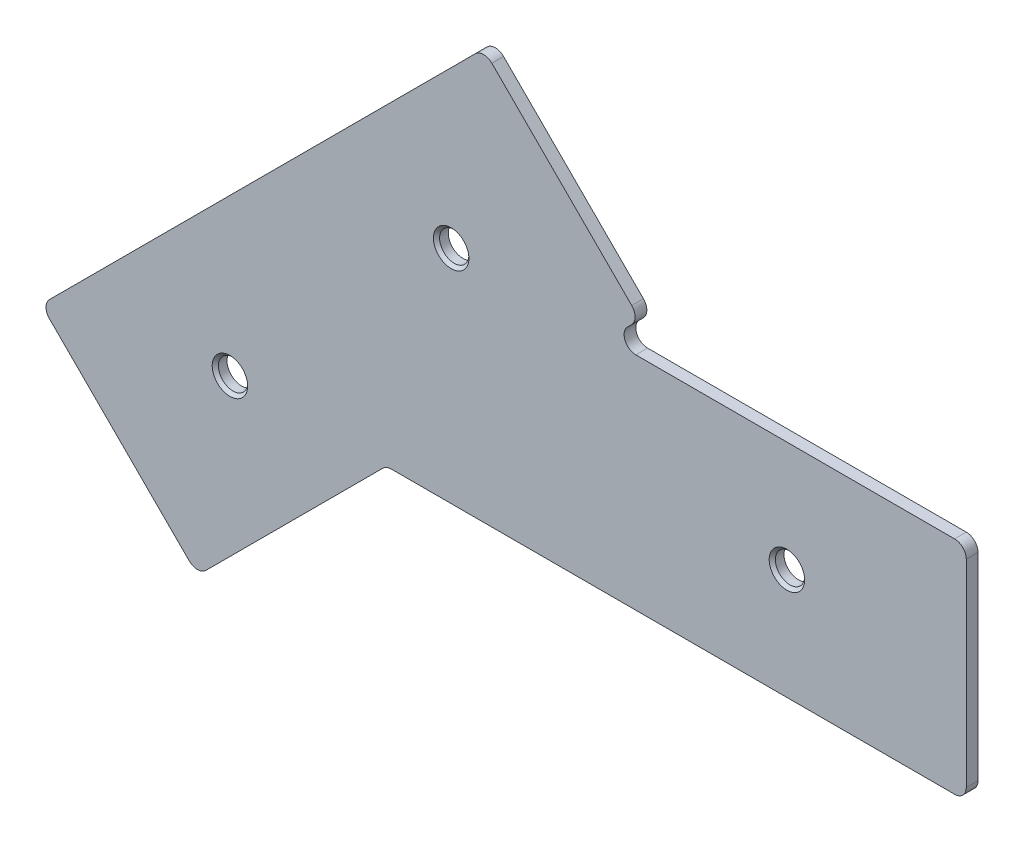
SolidWorks part; units mm, degrees
ref_plane "Front Plane" through (0, 0, 0) normal (0, 0, 1) x (1, 0, 0)
ref_plane "Top Plane" through (0, 0, 0) normal (0, 1, 0) x (1, 0, 0)
ref_plane "Right Plane" through (0, 0, 0) normal (1, 0, 0) x (0, 0, -1)
sketch "Sketch1" plane through (0, 0, 0) normal (0, 0, 1) x (1, 0, 0)
  line L0 (0, 0) -> (75.519, 75.519) construction
  line L1 (0, 0) -> (75.519, 0) construction
  line L2 (75.519, 75.519) -> (75.519, 0) construction
  line L3 (37.7595, 37.7595) -> (144.5595, 37.7595) construction
  line L4 (13.3466, -13.3466) -> (45.5778, 18.8845)
  line L5 (45.5778, 18.8845) -> (144.5595, 18.8845)
  line L6 (-13.3466, 13.3466) -> (62.1724, 88.8656)
  line L7 (37.7595, 18.8845) -> (144.5595, 18.8845) construction
  line L8 (83.3278, 56.6345) -> (144.5595, 56.6345)
  line L9 (83.3278, 56.6345) -> (88.8656, 62.1724)
  line L10 (13.3466, -13.3466) -> (88.8656, 62.1724) construction
  line L11 (-13.3466, 13.3466) -> (13.3466, -13.3466)
  line L12 (62.1724, 88.8656) -> (88.8656, 62.1724)
  line L13 (144.5595, 56.6345) -> (144.5595, 18.8845)
  dimension "D1" = 135
  dimension "D2" = 106.8
  dimension "D3" = 106.8
  dimension "D4" = 18.875
  dimension "D6" = 61.2317
  dimension "D5" = 18.875
base flange "Base-Flange1" sketch "Sketch1" thickness 2 reverse thickness direction no parameters "D1"=2
sketch "Sketch6" plane through (0, 0, 0) normal (0, 0, 1) x (1, 0, 0)
  line L0 (0, 0) -> (75.519, 75.519) construction
  line L1 (88.8656, 62.1724) -> (62.1724, 88.8656) construction
  line L2 (144.5595, 37.7595) -> (11.0662, 37.7595) construction
  line L3 (144.5595, 18.8845) -> (144.5595, 56.6345) construction
  line L4 (62.1724, 88.8656) -> (-13.3466, 13.3466) construction
  line L5 (32.2264, 5.5331) -> (5.5331, 32.2264) construction
  line L6 (13.3466, -13.3466) -> (45.5778, 18.8845) construction
  line L7 (-13.3466, 13.3466) -> (13.3466, -13.3466) construction
  line L8 (43.2926, 69.9859) -> (69.9859, 43.2926) construction
  line L9 (83.3278, 56.6345) -> (88.8656, 62.1724) construction
  line L10 (113.9436, 56.6345) -> (113.9436, 18.8845) construction
  line L11 (144.5595, 56.6345) -> (83.3278, 56.6345) construction
  line L12 (45.5778, 18.8845) -> (144.5595, 18.8845) construction
  dimension "D1" = 26.7
  dimension "D2" = 26.7
sketch "Sketch10" plane through (0, 0, 0) normal (0, 0, 1) x (1, 0, 0)
  line L0 (43.2926, 69.9859) -> (69.9859, 43.2926) construction
  line L1 (32.2264, 5.5331) -> (5.5331, 32.2264) construction
  line L2 (113.9436, 56.6345) -> (113.9436, 18.8845) construction
  point P0 (56.6393, 56.6393)
  point P4 (18.8798, 18.8798)
  point P8 (113.9436, 37.7595)
hole_wizard "M6x1.0 Tapped Hole1" positions "Sketch10" profile "Sketch8" tap size "M6x1.0" standard "ANSI Metric"
sketch "Sketch8" plane through (56.6393, 56.6393, 0) normal (1, 0, 0) x (0, -1, 0)
  line L0 (0, 0) -> (0, 16.5022)
  line L1 (0, 16.5022) -> (2.5, 15)
  line L2 (2.5, 15) -> (2.5, 0.525)
  line L3 (2.5, 0.525) -> (3.025, 0)
  line L5 (3.025, 0) -> (0, 0)
  line L6 (-2.5, 0.525) -> (-3.025, 0) construction
  line L10 (0, 16.5022) -> (-2.5, 15) construction
  line L11 (0, -6.35) -> (0, 107.95) construction
  dimension "Tap Drill Dia." = 5
  dimension "Tap Drill Depth" = 15
  dimension "Near C'Sink Dia." = 6.05
  dimension "Near C'Sink Angle" = 90
  dimension "Drill Angle" = 118
cosmetic thread "Hole Thread1"
cosmetic thread "Hole Thread2"
cosmetic thread "Hole Thread3"
fillet "Fillet1" radius 2 8 edges at (62.1724, 88.8656, -1) (-13.3466, 13.3466, -1) (13.3466, -13.3466, -1) (45.5778, 18.8845, -1) (144.5595, 18.8845, -1) (144.5595, 56.6345, -1) (88.8656, 62.1724, -1) (83.3278, 56.6345, -1)
sketch "Bend-Lines1" [suppressed] plane through (0, 0, 0) normal (0, 1, 0) x (1, 0, 0)
sketch "Bounding-Box1" [suppressed] plane through (0, 0, 0) normal (0, 1, 0) x (1, 0, 0)
sheet metal parameters "Sheet-Metal1" thickness 2 parameters "D1"=2
flat pattern "Flat-Pattern1" [suppressed]
sketch "Bend-Lines2" plane through (0, 0, 0) normal (0, 1, 0) x (1, 0, 0)
sketch3d "Bounding-Box2" [suppressed]
  line L0 (-5.1817, -17.0787, 0) -> (152.7198, 21.2955, 0) construction
  line L1 (-25.56, 66.7736, 0) -> (132.3415, 105.1478, 0) construction
  line L2 (-5.1817, -17.0787, 0) -> (-25.56, 66.7736, 0) construction
  line L3 (152.7198, 21.2955, 0) -> (132.3415, 105.1478, 0) construction
sheet metal parameters "Sheet-Metal2" thickness 2 parameters "D1"=2
flat pattern "Flat-Pattern1"
sketch "Bend-Lines2" plane through (0, 0, 0) normal (0, 1, 0) x (1, 0, 0)
sketch3d "Bounding-Box2" [suppressed]
  line L0 (-5.1817, -17.0787, 0) -> (152.7198, 21.2955, 0) construction
  line L1 (-25.56, 66.7736, 0) -> (132.3415, 105.1478, 0) construction
  line L2 (-5.1817, -17.0787, 0) -> (-25.56, 66.7736, 0) construction
  line L3 (152.7198, 21.2955, 0) -> (132.3415, 105.1478, 0) construction
